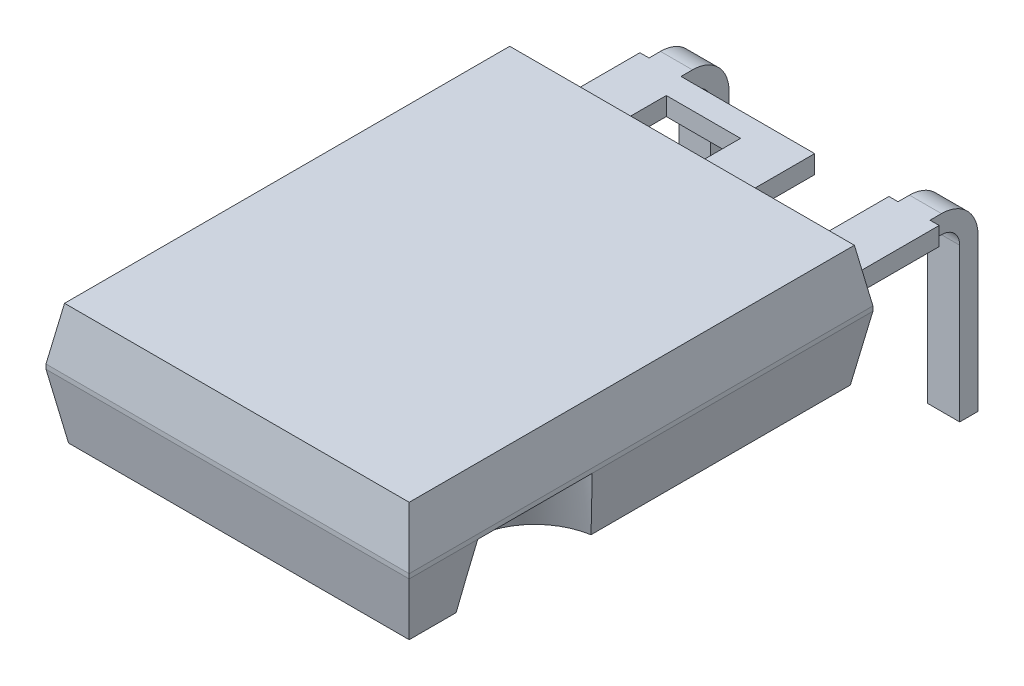
SolidWorks part; units mm, degrees
ref_plane "Front" through (0, 0, 0) normal (0, 0, 1) x (1, 0, 0)
ref_plane "Top" through (0, 0, 0) normal (0, 1, 0) x (1, 0, 0)
ref_plane "Right" through (0, 0, 0) normal (1, 0, 0) x (0, 0, -1)
sketch "Эскиз1" plane through (0, 0, 0) normal (0, 0, 1) x (1, 0, 0)
  line L1 (-6.95, -1.5) -> (-3.95, -1.5)
  line L2 (-6.95, -1.5) -> (-6.95, 1.5)
  line L3 (-6.95, 1.5) -> (-3.95, 1.5)
  line L4 (-3.95, -1.5) -> (-3.95, 1.5)
  line L5 (-1.5, -1.5) -> (1.5, -1.5)
  line L6 (-1.5, -1.5) -> (-1.5, 1.5)
  line L7 (-1.5, 1.5) -> (1.5, 1.5)
  line L8 (1.5, -1.5) -> (1.5, 1.5)
  line L9 (3.95, -1.5) -> (6.95, -1.5)
  line L10 (3.95, -1.5) -> (3.95, 1.5)
  line L11 (3.95, 1.5) -> (6.95, 1.5)
  line L12 (6.95, -1.5) -> (6.95, 1.5)
ref_plane "Плоскость1" through (0, 0, 4.3) normal (0, 0, 1) x (1, 0, 0)
sketch "Эскиз3" plane through (0, 0, 4.3) normal (0, 0, 1) x (1, 0, 0)
  line L0 (-7.95, -2.8) -> (-7.95, 2.5)
  line L1 (7.95, 2.5) -> (7.95, -2.8)
  line L2 (7.95, -2.8) -> (-7.95, -2.8)
  line L3 (-7.95, 2.5) -> (7.95, 2.5)
  dimension "D1" = 2.5
  dimension "D2" = 7.95
  dimension "D3" = 15.9
  dimension "D4" = 5.3
extrude "Вытянуть1" add sketch "Эскиз3" along normal blind 20.3
sketch "Эскиз4" plane through (0, 0, 0) normal (0, 0, 1) x (1, 0, 0)
  line L0 (-2.725, 3.0919) -> (-2.725, -3.4869) construction
  line L1 (1.1, 0.4) -> (-1.1, 0.4)
  line L2 (1.1, 0.4) -> (1.1, -0.4)
  line L3 (1.1, -0.4) -> (-1.1, -0.4)
  line L4 (-1.1, 0.4) -> (-1.1, -0.4)
  line L5 (-4.35, 0.4) -> (-4.35, -0.4)
  line L6 (-6.55, -0.4) -> (-4.35, -0.4)
  line L7 (-6.55, 0.4) -> (-6.55, -0.4)
  line L8 (-6.55, 0.4) -> (-4.35, 0.4)
  line L9 (2.725, 3.5037) -> (2.725, -4.3048) construction
  line L10 (6.55, 0.4) -> (6.55, -0.4)
  line L11 (4.35, -0.4) -> (6.55, -0.4)
  line L12 (4.35, 0.4) -> (4.35, -0.4)
  line L13 (4.35, 0.4) -> (6.55, 0.4)
  dimension "D1" = 0.4
  dimension "D2" = 0.8
  dimension "D3" = 1.1
  dimension "D4" = 2.2
  dimension "D5" = 5.45
  dimension "D6" = 5.45
extrude "Вытянуть2" add sketch "Эскиз4" along normal up to surface (4.3 mm away) up to face at (0, -0.15, 4.3)
sketch "Эскиз6" plane through (0, 0, 0) normal (0, 0, 1) x (1, 0, 0)
  line L0 (1.1, 0.4) -> (-1.1, 0.4) construction
  line L1 (0.7, 0.4) -> (-0.7, 0.4)
  line L2 (0.7, 0.4) -> (0.7, -0.4)
  line L3 (0.7, -0.4) -> (-0.7, -0.4)
  line L4 (-0.7, 0.4) -> (-0.7, -0.4)
  line L5 (-1.1, -0.4) -> (1.1, -0.4) construction
  line L6 (-2.725, 2.7944) -> (-2.725, -3.0786) construction
  line L7 (-4.75, 0.4) -> (-4.75, -0.4)
  line L8 (-6.15, -0.4) -> (-4.75, -0.4)
  line L9 (-6.15, 0.4) -> (-6.15, -0.4)
  line L10 (-6.15, 0.4) -> (-4.75, 0.4)
  line L11 (2.725, 2.9597) -> (2.725, -3.4981) construction
  line L12 (6.15, 0.4) -> (6.15, -0.4)
  line L13 (4.75, -0.4) -> (6.15, -0.4)
  line L14 (4.75, 0.4) -> (4.75, -0.4)
  line L15 (4.75, 0.4) -> (6.15, 0.4)
  dimension "D1" = 0.7
  dimension "D2" = 1.4
  dimension "D3" = 5.45
  dimension "D4" = 5.45
extrude "Вытянуть3" add sketch "Эскиз6" against normal blind 10.5
sketch "Эскиз7" plane through (0, -2.8, 0) normal (0, -1, 0) x (1, 0, 0)
  line L0 (-7.95, 24.6) -> (7.95, 24.6) construction
  line L1 (-7.95, 24.6) -> (-7.95, 4.3) construction
  line L2 (-8.5805, 19.1) -> (9.0264, 19.1) construction
  line L4 (7.95, 16.6) -> (7.95, 21.6)
  line L5 (7.95, 24.6) -> (7.95, 4.3) construction
  line L6 (0, 25.0412) -> (0, 10.8871) construction
  line L7 (-7.95, 16.6) -> (-7.95, 21.6)
  circle A0 centre (0, 19.1) radius 1.8
  arc A1 (7.95, 21.6) -> (7.95, 16.6) centre (7.95, 19.1) ccw
  arc A2 (-7.95, 21.6) -> (-7.95, 16.6) centre (-7.95, 19.1) cw
  dimension "D3" = 3.6
  dimension "D4" = 2.5
  dimension "D1" = 5.5
  dimension "D2" = 7.95
extrude "Вырез-Вытянуть1" cut sketch "Эскиз7" against normal blind 2.8
sketch "Эскиз8" plane through (0, -2.8, 0) normal (0, -1, 0) x (1, 0, 0)
  circle A0 centre (-5, 7) radius 1
extrude "Вырез-Вытянуть2" cut sketch "Эскиз8" against normal blind 0.1
chamfer "Фаска1" distance 2.8 angle 10 8 edges at (0, -2.8, 4.3) (-7.95, -2.8, 10.45) (-5.45, -2.8, 19.1) (-7.95, -2.8, 23.1) (0, -2.8, 24.6) (7.95, -2.8, 23.1) (7.95, -2.8, 10.45) (5.45, -2.8, 19.1) first distance on face at (-5.45, 0, 4.3) first distance on face at (-7.95, -0.775, 16.775) first distance on face at (-6.7, -1.4, 19.1) first distance on face at (0, -0.15, 24.6) first distance on face at (7.95, -0.775, 16.775) first distance on face at (6.7, -1.4, 19.1)
chamfer "Фаска2" distance 2.3 angle 10 4 edges at (7.95, 2.5, 14.45) (0, 2.5, 24.6) (-7.95, 2.5, 14.45) (0, 2.5, 4.3) first distance on face at (7.95, 0.8333, 16) first distance on face at (0, 1.25, 24.6) first distance on face at (-7.95, 0.8333, 16) first distance on face at (0, 0.4625, 4.3)
sketch "Эскиз9" plane through (0, 0, -10.5) normal (0, 0, -1) x (-1, 0, 0)
  line L4 (-0.7, 0.4) -> (-0.7, -0.4)
  line L5 (-0.7, -0.4) -> (0.7, -0.4)
  line L6 (0.7, -0.4) -> (0.7, 0.4)
  line L7 (0.7, 0.4) -> (-0.7, 0.4)
  line L8 (-0.7, 0.4) -> (-0.7, -0.4)
  line L9 (-0.7, -0.4) -> (0.7, -0.4)
  line L10 (0.7, -0.4) -> (0.7, 0.4)
  line L11 (0.7, 0.4) -> (-0.7, 0.4)
  dimension "D1" = 0
extrude "Вырез-Вытянуть3" cut sketch "Эскиз9" against normal up to surface (10.5 mm away) up to face at (-0.9, 0.1, 0)
sketch "Эскиз10" plane through (-1.1, 0, 0) normal (-1, 0, 0) x (0, 0, 1)
  line L0 (1.0451, 0.4) -> (1.0451, -0.4)
  line L6 (0, -0.4) -> (4.3705, -0.4)
  line L7 (4.3705, -0.4) -> (4.3, 0)
  line L8 (4.3, 0) -> (4.3, 0.2)
  line L9 (4.3, 0.2) -> (4.3353, 0.4)
  line L10 (4.3353, 0.4) -> (0, 0.4)
  line L11 (0, 0.4) -> (0, -0.4)
  line L12 (0, -0.4) -> (1.0451, -0.4)
  line L16 (1.0451, 0.4) -> (0, 0.4)
  line L17 (0, 0.4) -> (0, -0.4)
  dimension "D1" = 0
extrude "Вытянуть4" add sketch "Эскиз10" along normal up to surface (3.25 mm away) up to face at (-4.35, 0.0333, 2.8843)
sketch "Эскиз11" plane through (0, -0.4, 0) normal (0, -1, 0) x (1, 0, 0)
  line L0 (-6.15, -10.5) -> (-6.15, 0) construction
  line L1 (-6.15, -2.1) -> (-4.75, -2.1)
  line L2 (-6.15, -2.1) -> (-6.15, -1.3)
  line L3 (-6.15, -1.3) -> (-4.75, -1.3)
  line L4 (-4.75, -2.1) -> (-4.75, -1.3)
  line L5 (-4.75, -10.5) -> (-4.75, 0) construction
  line L6 (4.75, -10.5) -> (4.75, 0) construction
  line L7 (4.75, -1.3) -> (6.15, -1.3)
  line L8 (4.75, -1.3) -> (4.75, -2.1)
  line L9 (4.75, -2.1) -> (6.15, -2.1)
  line L10 (6.15, -1.3) -> (6.15, -2.1)
  line L11 (6.15, -10.5) -> (6.15, 0) construction
  line L12 (-6.55, 4.3) -> (-7.95, 4.3) construction
  dimension "D1" = 5.6
  dimension "D2" = 0.8
extrude "Вытянуть5" add sketch "Эскиз11" along normal blind 7.5
sketch "Эскиз12" plane through (0, 0, -10.5) normal (0, 0, -1) x (-1, 0, 0)
  line L4 (6.15, 0.4) -> (4.75, 0.4)
  line L5 (4.75, 0.4) -> (4.75, -0.4)
  line L6 (4.75, -0.4) -> (6.15, -0.4)
  line L7 (6.15, -0.4) -> (6.15, 0.4)
  line L8 (6.15, 0.4) -> (4.75, 0.4)
  line L9 (4.75, 0.4) -> (4.75, -0.4)
  line L10 (4.75, -0.4) -> (6.15, -0.4)
  line L11 (6.15, -0.4) -> (6.15, 0.4)
  line L12 (-4.75, 0.4) -> (-6.15, 0.4)
  line L13 (-6.15, 0.4) -> (-6.15, -0.4)
  line L14 (-6.15, -0.4) -> (-4.75, -0.4)
  line L15 (-4.75, -0.4) -> (-4.75, 0.4)
  line L16 (-4.75, 0.4) -> (-6.15, 0.4)
  line L17 (-6.15, 0.4) -> (-6.15, -0.4)
  line L18 (-6.15, -0.4) -> (-4.75, -0.4)
  line L19 (-4.75, -0.4) -> (-4.75, 0.4)
  dimension "D1" = 0
  dimension "D2" = 0
extrude "Вырез-Вытянуть4" cut sketch "Эскиз12" against normal up to surface (8.4 mm away) up to face at (-5.45, -4.15, -2.1)
fillet "Скругление1" radius 0.8 2 edges at (5.45, -0.4, -1.3) (-5.45, -0.4, -1.3)
fillet "Скругление2" radius 1.6 2 edges at (5.45, 0.4, -2.1) (-5.45, 0.4, -2.1)
sketch "Эскиз13" plane through (0, -7.9, 0) normal (0, -1, 0) x (1, 0, 0)
  line L0 (-5.45, -1.7) -> (-4.4502, -1.7) construction
  line L1 (-5.45, -1.7) -> (-5.45, -0.9225) construction
  line L2 (-6.15, -1.3) -> (-6.15, -2.1) construction
  line L3 (-4.75, -2.1) -> (-4.75, -1.3) construction
  line L4 (-4.75, -1.3) -> (-6.15, -1.3) construction
  line L5 (-6.15, -2.1) -> (-4.75, -2.1) construction
  circle A0 centre (-5.45, -1.7) radius 0.1779
extrude "Вырез-Вытянуть5" cut sketch "Эскиз13" against normal blind 4
